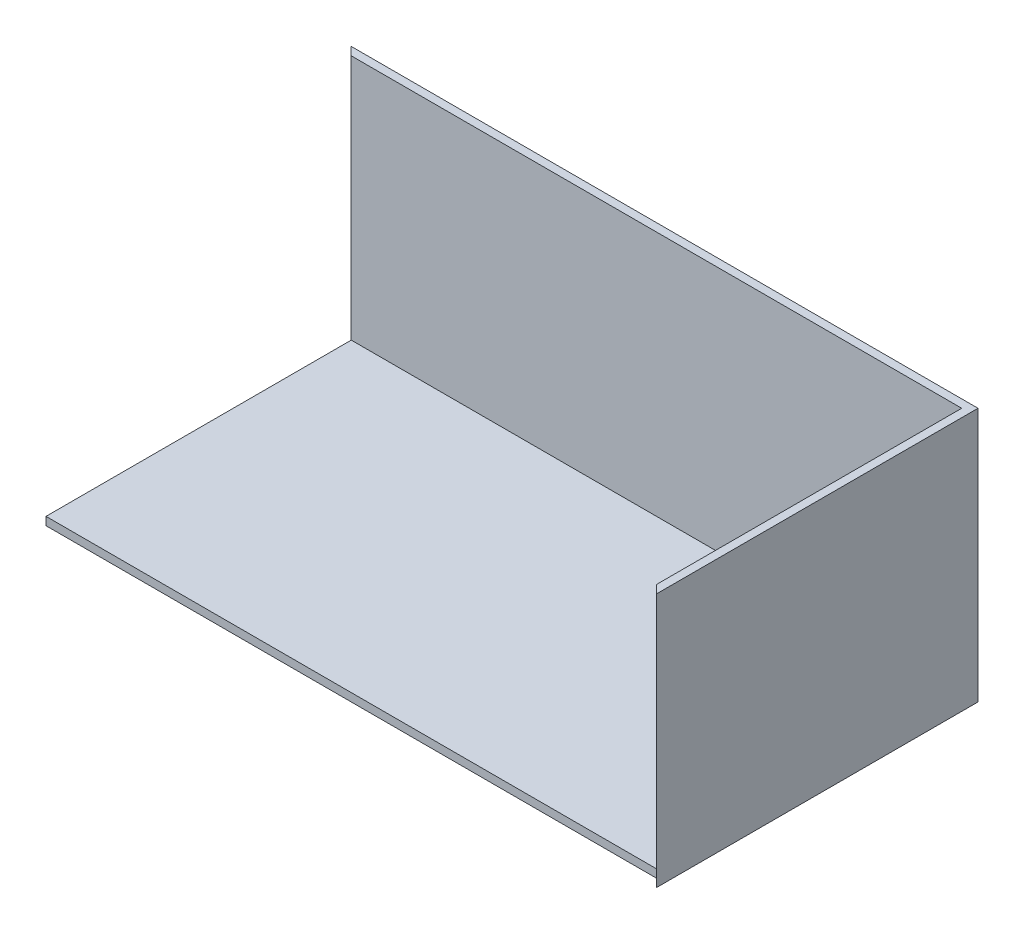
SolidWorks part; units mm, degrees
ref_plane "Front Plane" through (0, 0, 0) normal (0, 0, 1) x (1, 0, 0)
ref_plane "Top Plane" through (0, 0, 0) normal (0, 1, 0) x (1, 0, 0)
ref_plane "Right Plane" through (0, 0, 0) normal (1, 0, 0) x (0, 0, -1)
sketch "Sketch2" plane through (0, 0, 0) normal (0, 1, 0) x (1, 0, 0)
  line L0 (-300, -150) -> (-308, -158)
  line L5 (-308, 158) -> (308, 158)
  line L6 (-308, 158) -> (-308, -158)
  line L7 (-300, 150) -> (300, 150)
  line L8 (-300, 150) -> (-300, -150)
  line L9 (-300, -150) -> (300, -150)
  line L10 (300, 150) -> (300, -150)
  line L11 (-300, 150) -> (300, -150) construction
  line L12 (-300, -150) -> (300, 150) construction
  line L13 (-308, -158) -> (308, -158)
  line L14 (308, 158) -> (308, -158)
  line L15 (-308, 158) -> (308, -158) construction
  line L16 (-308, -158) -> (308, 158) construction
  line L17 (-300, 150) -> (-308, 158)
  line L18 (300, 150) -> (308, 158)
  line L19 (300, -150) -> (308, -158)
  point P0 (0, 0)
  point P6 (0, 0)
  dimension "D1" = 600
  dimension "D2" = 300
  dimension "D3" = 8
  dimension "D4" = 8
extrude "Boss-Extrude2" add sketch "Sketch2" along normal blind 250 contours L7 L18 L5 L17 | L10 L19 L14 L18 region at (0, 0, -154.0175) region at (304.0346, 0, 0)
extrude "Boss-Extrude3" add sketch "Sketch2<8>" along normal blind 8 contours L10 L7 L8 L9 region at (0, 0, 0)
sketch "Sketch2<8>" plane through (0, 0, 0) normal (0, 1, 0) x (1, 0, 0) same geometry as "Sketch2"
